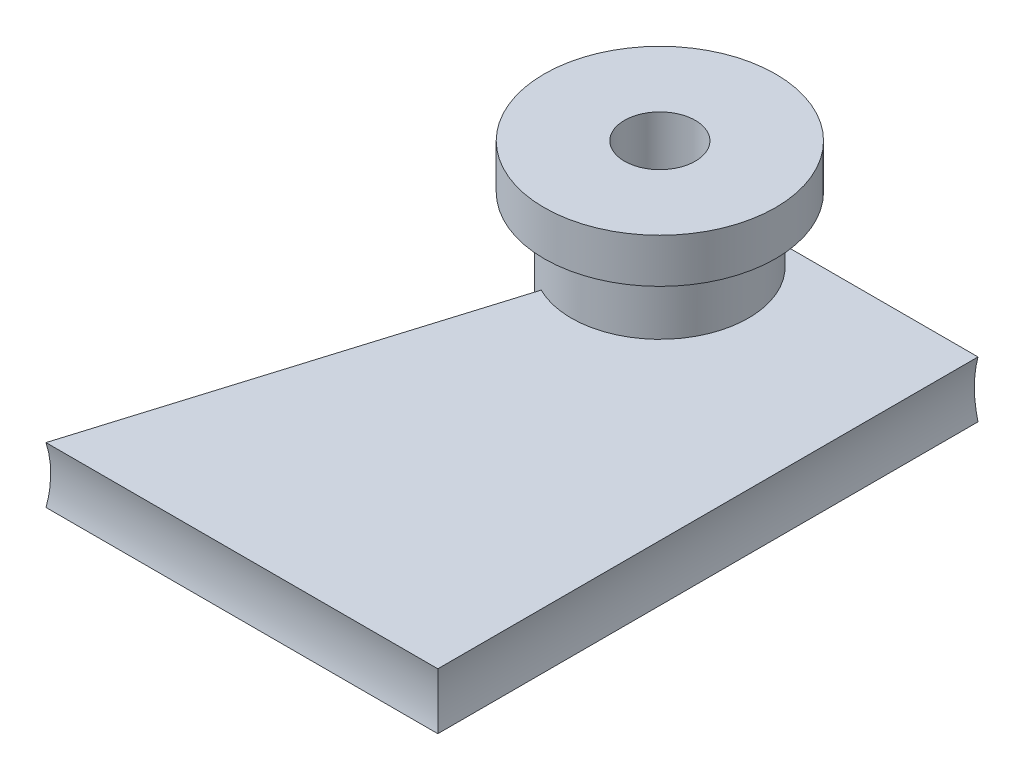
SolidWorks part; units mm, degrees
ref_plane "Front Plane" through (0, 0, 0) normal (0, 0, 1) x (1, 0, 0)
ref_plane "Top Plane" through (0, 0, 0) normal (0, 1, 0) x (1, 0, 0)
ref_plane "Right Plane" through (0, 0, 0) normal (1, 0, 0) x (0, 0, -1)
sketch "Sketch1" plane through (0, 0, 0) normal (0, 1, 0) x (1, 0, 0)
  line L6 (30.8201, 40.3482) -> (30.8201, -20.6518)
  line L8 (30.8201, -20.6518) -> (-13.4276, -20.6518)
  line L9 (42.9102, -20.6518) -> (-457.0898, -20.6518) construction
  line L10 (-13.4276, -20.6518) -> (-0.3778, 22.217)
  line L13 (30.8201, 40.3482) -> (8.048, 40.3482)
  circle A0 centre (4.0692, 31.1738) radius 4
  circle A1 centre (4.0692, 31.1738) radius 10
  dimension "D2" = 20
  dimension "D3" = 8
  dimension "D1" = 61
extrude "Boss-Extrude1" add sketch "Sketch1" along normal blind 6.35 contours A1 region at (13.4735, 0, -4.9197)
extrude "Boss-Extrude2" add sketch "Sketch1<3>" along normal blind 18.7 contours A1 A0 | A1 A0 region at (12.193, 0, -36.5055)
sketch "Sketch1<3>" plane through (0, 0, 0) normal (0, 1, 0) x (1, 0, 0) same geometry as "Sketch1"
ref_plane "Plane1" through (0, 9.35, 0) normal (0, 1, 0) x (1, 0, 0)
sketch "Sketch3" plane through (0, 0, 0) normal (0, 0, 1) x (1, 0, 0)
  line L0 (30.8201, 3.175) -> (121.9702, 3.175) construction
  line L1 (30.8201, 6.35) -> (30.8201, 0) construction
  circle A0 centre (42.9102, 3.175) radius 12.5
  dimension "D1" = 25
extrude "Cut-Extrude1" cut sketch "Sketch3" against normal through all both and the other way through all
sketch "Sketch4" plane through (0, 0, 0) normal (1, 0, 0) x (0, 0, -1)
  line L0 (-35.1146, 3.175) -> (-60.5591, 3.175) construction
  circle A0 centre (-32.7419, 3.175) radius 12.5
  dimension "D1" = 25
extrude "Cut-Extrude3" cut sketch "Sketch4" along normal through all both and the other way through all
sketch "Sketch5" plane through (0, 18.7, 0) normal (0, 1, 0) x (1, 0, 0)
  line L0 (-9, 31.1738) -> (-9, -41.5829)
  line L5 (0, -31.4363) -> (0, 0)
  line L6 (11.1107, 24.0732) -> (57.0761, 17.1692)
  line L7 (-9, -41.5829) -> (28.6441, -41.5829)
  line L8 (44.2561, 19.0948) -> (44.2561, 3.9832)
  line L9 (0, 0) -> (6.2423, 0)
  line L12 (17.595, -31.4363) -> (0, -31.4363)
  line L13 (11.4551, 8.4817) -> (15.2018, 18.1471)
  line L14 (15.2018, 18.1471) -> (36.949, 13.3144)
  line L15 (36.949, 13.3144) -> (28.816, -1.1837)
  line L16 (28.816, -1.1837) -> (11.4551, 8.4817)
  line L17 (6.2423, 0) -> (17.595, -31.4363)
  circle A0 centre (4.0692, 31.1738) radius 10 construction
  circle A1 centre (4.0692, 31.1738) radius 4
  circle A2 centre (4.0692, 31.1738) radius 13.0692
  arc A4 (57.0761, 17.1692) -> (28.6441, -41.5829) centre (105.0586, -42.3067) ccw
  circle M6 centre (4.0692, 31.1738) radius 10
extrude "Boss-Extrude3" add sketch "Sketch5" against normal blind 5 contours M6 region at (4.0692, 18.7, -43.8733)
